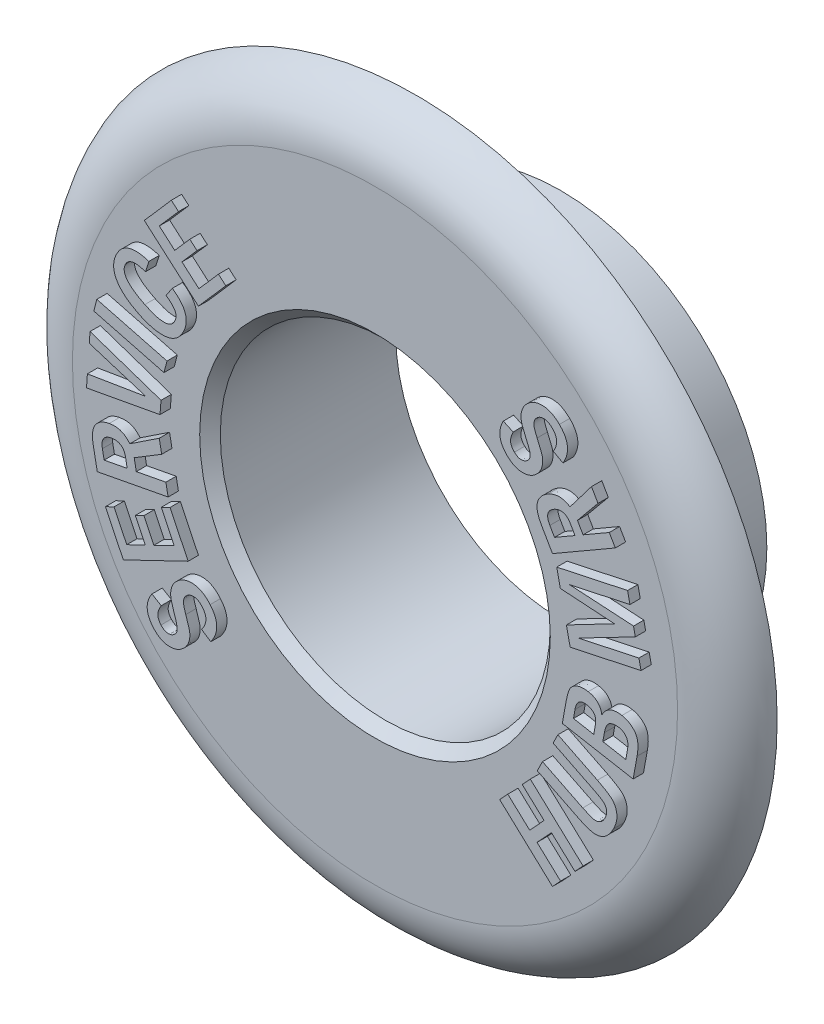
SolidWorks part; units mm, degrees
ref_plane "Plan de face" through (0, 0, 0) normal (0, 0, 1) x (1, 0, 0)
ref_plane "Plan de dessus" through (0, 0, 0) normal (0, 1, 0) x (1, 0, 0)
ref_plane "Plan de droite" through (0, 0, 0) normal (1, 0, 0) x (0, 0, -1)
sketch "Esquisse1" plane through (0, 0, 0) normal (0, 0, 1) x (1, 0, 0)
  circle A0 centre (0, 0) radius 8
  circle A1 centre (0, 0) radius 10
  dimension "D1" = 16
  dimension "D2" = 20
extrude "Boss.-Extru.1" add sketch "Esquisse1" along normal blind 7
sketch "Esquisse2" plane through (0, 0, 7) normal (0, 0, 1) x (1, 0, 0)
  circle A0 centre (0, 0) radius 17.5
  circle A1 centre (0, 0) radius 8
  dimension "D1" = 35
extrude "Boss.-Extru.2" add sketch "Esquisse2" along normal blind 2
fillet "Congé1" radius 3 1 edges at (17.5, 0, 9)
chamfer "Chanfrein1" distance 0.5 angle 45 1 edges at (8, 0, 9)
sketch "Esquisse3" plane through (0, 0, 9) normal (0, 0, 1) x (1, 0, 0)
  line L0 (0, 0) -> (14.6716, 0) construction
  circle A0 centre (0, 0) radius 10 construction
  circle A1 centre (0, 0) radius 13.5 construction
  circle A2 centre (0, 0) radius 14.6716 construction
  text T0 "SERVICE" font "Franklin Gothic Medium Cond" height 3.5
  text T1 "H U B " font "Franklin Gothic Medium Cond" height 3.5
  text T2 " M R S" font "Franklin Gothic Medium Cond" height 3.5
  dimension "D1" = 27
  dimension "D2" = 20
extrude "Boss.-Extru.3" add sketch "Esquisse3" along normal blind 0.5
